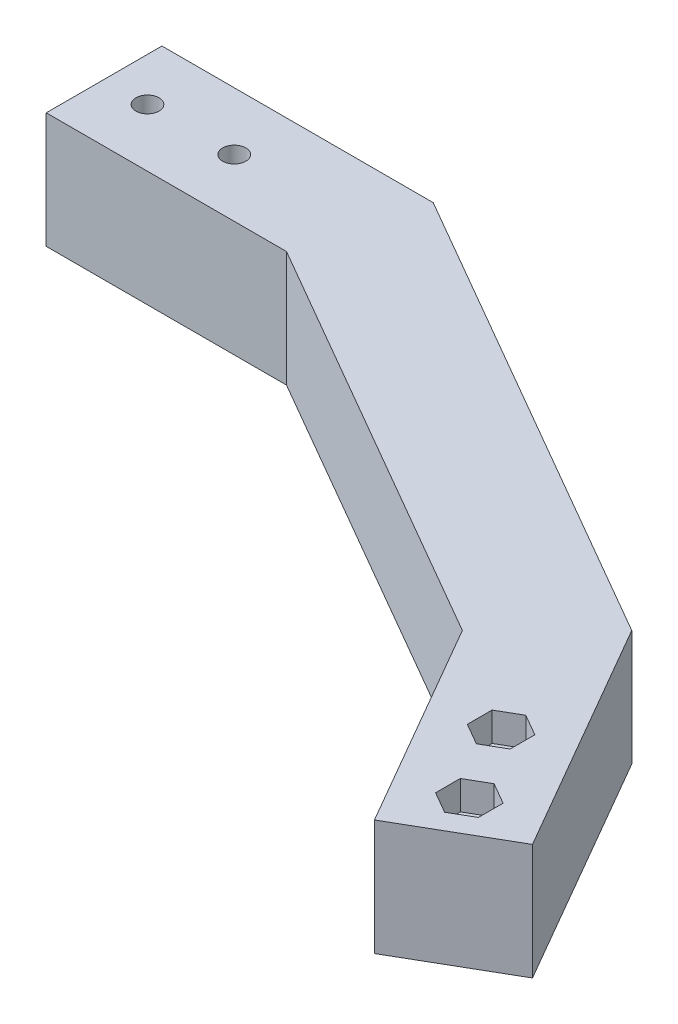
SolidWorks part; units mm, degrees
ref_plane "Front Plane" through (0, 0, 0) normal (0, 0, 1) x (1, 0, 0)
ref_plane "Top Plane" through (0, 0, 0) normal (0, 1, 0) x (1, 0, 0)
ref_plane "Right Plane" through (0, 0, 0) normal (1, 0, 0) x (0, 0, -1)
sketch "Sketch1" plane through (0, 0, 0) normal (0, 1, 0) x (1, 0, 0)
  line L0 (0, 155) -> (0, 175)
  line L1 (0, 175) -> (46.8911, 175)
  line L2 (46.8911, 175) -> (128.1089, 128.1089)
  line L3 (0, 0) -> (221.2337, 383.1881) construction
  line L4 (0, 155) -> (41.5321, 155)
  line L5 (41.5321, 155) -> (113.4679, 113.4679)
  line L6 (134.2339, 77.5) -> (113.4679, 113.4679)
  line L7 (151.5544, 87.5) -> (128.1089, 128.1089)
  line L8 (134.2339, 77.5) -> (151.5544, 87.5)
  line L9 (0, 155) -> (0, 150) construction
  circle A0 centre (0, 0) radius 150 construction
  dimension "D1" = 300
  dimension "D2" = 20
  dimension "D3" = 150
  dimension "D4" = 20
  dimension "D5" = 175
  dimension "D6" = 25
extrude "Boss-Extrude1" add sketch "Sketch1" along normal blind 20
sketch "Sketch2" plane through (0, 20, 0) normal (0, 1, 0) x (1, 0, 0)
  line L0 (87.5, 151.5544) -> (77.5, 134.2339) construction
  line L1 (128.1089, 128.1089) -> (46.8911, 175) construction
  line L2 (41.5321, 155) -> (113.4679, 113.4679) construction
  line L3 (41.5321, 155) -> (41.5321, 175) construction
  line L4 (7.5, 160.7276) -> (11.2, 162.8638)
  line L5 (11.2, 162.8638) -> (11.2, 167.1362)
  line L6 (11.2, 167.1362) -> (7.5, 169.2724)
  line L7 (7.5, 169.2724) -> (3.8, 167.1362)
  line L8 (3.8, 167.1362) -> (3.8, 162.8638)
  line L9 (3.8, 162.8638) -> (7.5, 160.7276)
  line L10 (46.8911, 175) -> (0, 175) construction
  line L11 (41.5321, 165) -> (0, 165) construction
  line L12 (0, 175) -> (0, 155) construction
  line L13 (122.1281, 118.4679) -> (142.8942, 82.5) construction
  line L14 (22.5, 169.2724) -> (18.8, 167.1362)
  line L15 (18.8, 167.1362) -> (18.8, 162.8638)
  line L16 (18.8, 162.8638) -> (22.5, 160.7276)
  line L17 (22.5, 160.7276) -> (26.2, 162.8638)
  line L18 (26.2, 162.8638) -> (26.2, 167.1362)
  line L19 (26.2, 167.1362) -> (22.5, 169.2724)
  line L20 (113.4679, 113.4679) -> (130.7884, 123.4679) construction
  line L21 (131.6442, 106.258) -> (135.3442, 104.1218)
  line L22 (127.9442, 104.1218) -> (131.6442, 106.258)
  line L23 (127.9442, 99.8494) -> (127.9442, 104.1218)
  line L24 (131.6442, 97.7132) -> (127.9442, 99.8494)
  line L25 (135.3442, 99.8494) -> (131.6442, 97.7132)
  line L26 (135.3442, 104.1218) -> (135.3442, 99.8494)
  line L27 (139.1442, 84.7228) -> (135.4442, 86.859)
  line L28 (142.8442, 86.859) -> (139.1442, 84.7228)
  line L29 (142.8442, 91.1314) -> (142.8442, 86.859)
  line L30 (139.1442, 93.2676) -> (142.8442, 91.1314)
  line L31 (135.4442, 91.1314) -> (139.1442, 93.2676)
  line L32 (135.4442, 86.859) -> (135.4442, 91.1314)
  circle A0 centre (7.5, 165) radius 3.7 construction
  circle A1 centre (22.5, 165) radius 3.7 construction
  circle A2 centre (7.5, 165) radius 2
  circle A3 centre (22.5, 165) radius 2
  circle A4 centre (131.6442, 101.9856) radius 3.7 construction
  circle A5 centre (139.1442, 88.9952) radius 3.7 construction
  circle A6 centre (131.6442, 101.9856) radius 2
  circle A7 centre (139.1442, 88.9952) radius 2
  dimension "D4" = 4
  dimension "D1" = 7.4
  dimension "D2" = 7.5
  dimension "D3" = 15
extrude "Cut-Extrude1" cut sketch "Sketch2" against normal through all contours A2 | A3 | A6 | A7 region at (7.5, 20, -165) region at (22.5, 20, -165) region at (131.6442, 20, -101.9856)
extrude "Cut-Extrude2" cut sketch "Sketch2<3>" along normal blind 5 from surface contours L8 L9 L4 L5 L6 L7 A2 | L18 L19 L14 L15 L16 L17 A3 region at (5.7065, 20, -161.8936) region at (24.2935, 20, -168.1064) starting at face at (22.5, 0, -163)
sketch "Sketch2<3>" plane through (0, 20, 0) normal (0, 1, 0) x (1, 0, 0) same geometry as "Sketch2"
extrude "Cut-Extrude3" cut sketch "Sketch2<4>" against normal blind 5 contours L26 L21 L22 L23 L24 L25 A6 | L32 L27 L28 L29 L30 L31 A7 region at (133.4377, 20, -105.092) region at (137.3507, 20, -85.8888)
sketch "Sketch2<4>" plane through (0, 20, 0) normal (0, 1, 0) x (1, 0, 0) same geometry as "Sketch2"
